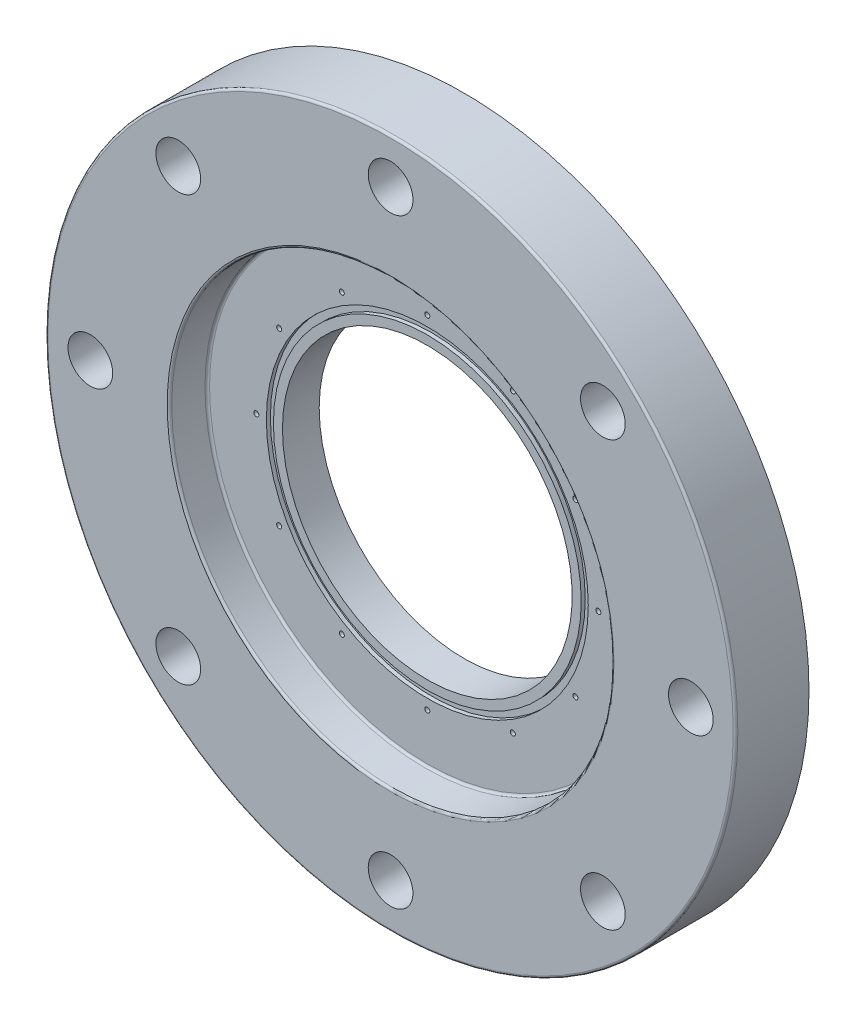
SolidWorks part; units mm, degrees
ref_plane "Front Plane" through (0, 0, 0) normal (0, 0, 1) x (1, 0, 0)
ref_plane "Top Plane" through (0, 0, 0) normal (0, 1, 0) x (1, 0, 0)
ref_plane "Right Plane" through (0, 0, 0) normal (1, 0, 0) x (0, 0, -1)
sketch "Sketch0" plane through (0, 0, 0) normal (1, 0, 0) x (0, 0, -1)
  line L0 (0, 0) -> (-36.5125, 0) construction
  point P3 (-36.5125, 0)
  point P4 (-5.5562, 0)
  dimension "Q" = 36.5125
  dimension "N" = 5.5562
sketch "Sketch1" plane through (0, 0, 0) normal (0, 0, 1) x (1, 0, 0)
  circle A0 centre (0, 0) radius 171.45
  circle A1 centre (0, 0) radius 109.9185 construction
  circle A2 centre (0, 0) radius 149.225 construction
  circle A3 centre (0, 149.225) radius 11.1125 construction
  circle A6 centre (0, 0) radius 109.347 construction
  point P9 (0, 109.9185)
  point P10 (0, 109.347)
  dimension "A" = 342.9
  dimension "B" = 298.45
  dimension "Bolt Hole Size" = 22.225
  dimension "Pipe OD A" = 219.837
  dimension "Pipe OD B" = 218.694
extrude "Extrude1" add sketch "Sketch1" along normal up to vertex (36.5125 mm away) up to point (0, 0, 36.5125)
sketch "Sketch2" plane through (0, 0, 36.5125) normal (0, 0, 1) x (1, 0, 0)
  circle A0 centre (0, 149.225) radius 11.1125 construction
  circle A1 centre (0, 149.225) radius 11.1125
extrude "Extrude2" cut sketch "Sketch2" against normal through all
ref_axis "Axis1" through (0, 0, -1.6272) along (0, 0, 1)
pattern_circular "CirPattern1" count 8 over 360 about axis through (0, 0, -1.6272) along (0, 0, 1) of "Extrude2"
sketch "Sketch3" plane through (0, 0, 0) normal (1, 0, 0) x (0, 0, -1)
  line L0 (-36.5125, 109.9185) -> (-18.2563, 109.347)
  line L1 (-18.2563, 109.347) -> (-18.2562, 0)
  line L2 (0, 0) -> (-36.5125, 0) construction
  line L3 (-18.2562, 0) -> (-36.5125, 0)
  line L4 (-36.5125, 0) -> (-36.5125, 109.9185)
  line L5 (0, 109.347) -> (-18.2563, 109.347) construction
  line L6 (-36.5125, 109.9185) -> (0, 109.9185) construction
revolve "Cut-Revolve1" cut sketch "Sketch3" angle 360 about L3
fillet "Fillet1" radius 1.1545 3 edges at (171.45, 0, 36.5125) (0, 109.347, 18.2563) (0, 109.9185, 36.5125) tangent propagation no
sketch "Sketch4" plane through (0, 0, 0) normal (0, 0, -1) x (-1, 0, 0)
  circle A0 centre (0, 0) radius 72
  dimension "D1" = 144
extrude "Cut-Extrude1" cut sketch "Sketch4" against normal blind 120 contours A0
sketch "Sketch5" plane through (0, 0, 18.2562) normal (0, 0, -1) x (-1, 0, 0)
  circle A0 centre (0, 0) radius 76.5
  circle A1 centre (0, 0) radius 80
  dimension "D1" = 153
  dimension "D2" = 160
sketch "Sketch6" plane through (0, 0, 18.2562) normal (0, 0, -1) x (-1, 0, 0)
  line L0 (0, 0) -> (0, 85) construction
  circle A0 centre (0, 0) radius 85 construction
  point P3 (0, 85)
  dimension "D1" = 170
hole_wizard "M3x0.5 Tapped Hole1" positions "Sketch7" profile "Sketch8" tap size "M3x0.5" standard "ANSI Metric"
sketch "Sketch7" plane through (0, 0, 18.2562) normal (0, 0, -1) x (-1, 0, 0)
  point P0 (0, 85)
sketch "Sketch8" plane through (0, 85, 18.2562) normal (1, 0, 0) x (0, -1, 0)
  line L0 (0, 0) -> (0, 12.7511)
  line L1 (0, 12.7511) -> (1.25, 12)
  line L2 (1.25, 12) -> (1.25, 0)
  line L5 (1.25, 0) -> (0, 0)
  line L10 (0, 12.7511) -> (-1.25, 12) construction
  line L11 (0, -6.35) -> (0, 107.95) construction
  dimension "Tap Drill Dia." = 2.5
  dimension "Tap Drill Depth" = 12
  dimension "Drill Angle" = 118
cosmetic thread "Hole Thread1" parameters "D1"=6, "D2"=3
sketch "Sketch9" plane through (0, 0, 0) normal (0, 1, 0) x (1, 0, 0)
  line L0 (0, 0) -> (0, 111.6244) construction
pattern_circular "CirPattern2" count 12 over 360 about axis through (0, 0, 0) along (0, 0, -1) of "M3x0.5 Tapped Hole1"
extrude "Cut-Extrude2" cut sketch "Sketch5" along normal blind 2
